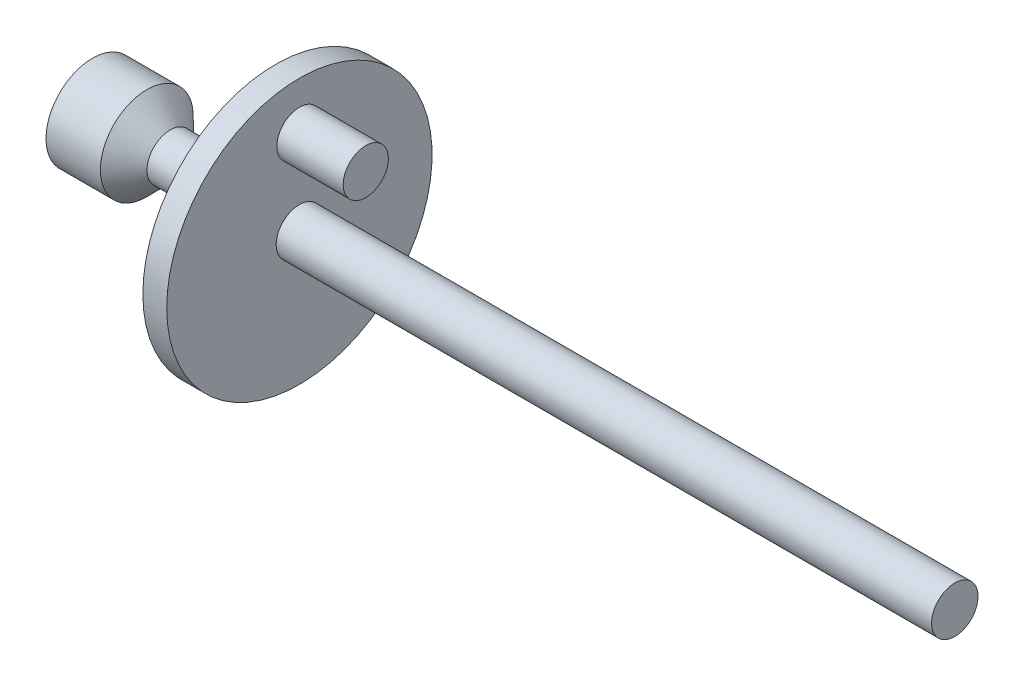
SolidWorks part; units mm, degrees
ref_plane "Plan de face" through (0, 0, 0) normal (0, 0, 1) x (1, 0, 0)
ref_plane "Plan de dessus" through (0, 0, 0) normal (0, 1, 0) x (1, 0, 0)
ref_plane "Plan de droite" through (0, 0, 0) normal (1, 0, 0) x (0, 0, -1)
sketch "Esquisse1" plane through (0, 0, 0) normal (0, 0, 1) x (1, 0, 0)
  line L0 (0, 0) -> (650, 0) construction
  line L1 (650, 0) -> (650, 17.5)
  line L2 (650, 17.5) -> (156, 17.5)
  line L3 (156, 17.5) -> (156, 100)
  line L4 (156, 100) -> (138, 100)
  line L5 (138, 100) -> (138, 17.5)
  line L6 (138, 17.5) -> (58.6, 17.5)
  line L7 (58.6, 17.5) -> (41, 35)
  line L8 (41, 35) -> (0, 35)
  line L9 (0, 35) -> (0, 0)
  line L10 (0, 0) -> (650, 0)
  dimension "D1" = 35
  dimension "D2" = 200
  dimension "D3" = 494
  dimension "D4" = 18
  dimension "D5" = 70
  dimension "D6" = 41
  dimension "D7" = 58.6
  dimension "D8" = 650
revolve "Révolution1" add sketch "Esquisse1" angle 360 about L0
sketch "Esquisse2" plane through (0, 0, 0) normal (0, 0, 1) x (1, 0, 0)
  line L0 (156, -100) -> (156, 100) construction
  line L1 (156, 81) -> (206, 81)
  line L2 (156, 81) -> (156, 64)
  line L4 (206, 81) -> (206, 64)
  line L5 (156, -17.5) -> (650, -17.5) construction
  line L6 (156, 64) -> (206, 64) construction
  line L7 (156, 64) -> (206, 64)
  dimension "D1" = 98.5
  dimension "D2" = 34
  dimension "D3" = 50
revolve "Révolution2" add sketch "Esquisse2" angle 360 about L6
sketch "Esquisse3" plane through (0, 0, 0) normal (-1, 0, 0) x (0, 0, 1)
  line L0 (-20, 20) -> (20, -20) construction
  line L1 (-20, 20) -> (20, 20)
  line L2 (-20, 20) -> (-20, -20)
  line L3 (-20, -20) -> (20, -20)
  line L4 (20, 20) -> (20, -20)
  point P4 (0, 0)
  dimension "D1" = 40
extrude "Enlèv. mat.-Extru.1" cut sketch "Esquisse3" against normal blind 25
extrude "Enlèv. mat.-Extru.2" cut sketch "Esquisse3<3>" against normal blind 25 draft 20 from surface starting at face at (25, 0, 0)
sketch "Esquisse3<3>" plane through (0, 0, 0) normal (-1, 0, 0) x (0, 0, 1) same geometry as "Esquisse3"
